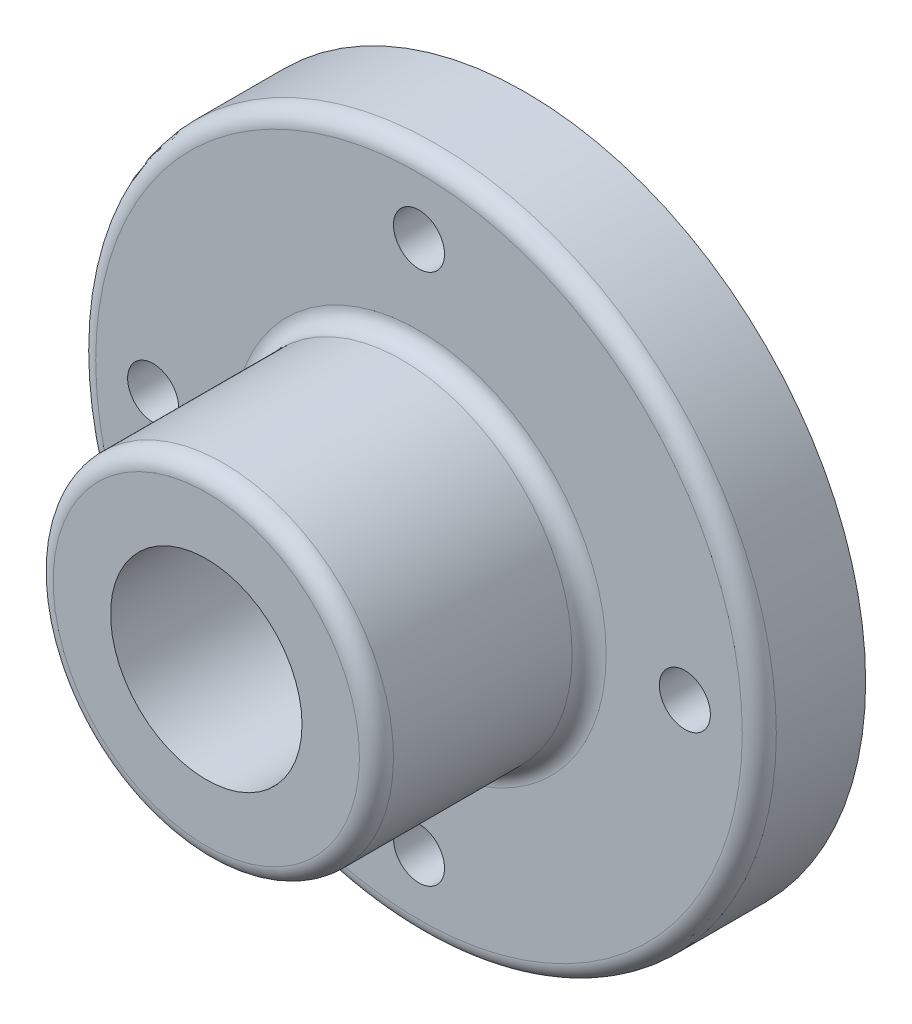
SolidWorks part; units mm, degrees
ref_plane "Plan de face" through (0, 0, 0) normal (0, 0, 1) x (1, 0, 0)
ref_plane "Plan de dessus" through (0, 0, 0) normal (0, 1, 0) x (1, 0, 0)
ref_plane "Plan de droite" through (0, 0, 0) normal (1, 0, 0) x (0, 0, -1)
sketch "Esquisse1" plane through (0, 0, 0) normal (0, 0, 1) x (1, 0, 0)
  line L0 (0, 62.5) -> (0, -62.5) construction
  line L1 (-62.5, 0) -> (62.5, 0) construction
  circle A0 centre (0, 0) radius 80
  circle A1 centre (0, 0) radius 40
  circle A2 centre (0, 0) radius 62.5
  circle A3 centre (0, 0) radius 22.5
  circle A4 centre (0, 62.5) radius 6
  circle A5 centre (-62.5, 0) radius 6
  circle A6 centre (62.5, 0) radius 6
  circle A7 centre (0, -62.5) radius 6
  point P4 (0, 0)
  point P12 (0, 0)
  point P15 (0, 0)
  point P22 (0, 0)
  point P23 (0, 0)
  dimension "D1" = 160
  dimension "D2" = 80
  dimension "D3" = 45
  dimension "D4" = 125
  dimension "D5" = 12
  dimension "D6" = 12
  dimension "D7" = 12
  dimension "D8" = 12
extrude "Base 25mm" add sketch "Esquisse1" along normal blind 25 contours A0
extrude "axe75mm" add sketch "Esquisse1<4>" along normal blind 75 contours A1
sketch "Esquisse1<4>" plane through (0, 0, 0) normal (0, 0, 1) x (1, 0, 0) same geometry as "Esquisse1"
extrude "Trou1" cut sketch "Esquisse1<5>" along normal up to next contours A4
sketch "Esquisse1<5>" plane through (0, 0, 0) normal (0, 0, 1) x (1, 0, 0) same geometry as "Esquisse1"
extrude "Trou2" cut sketch "Esquisse1<6>" along normal up to next contours A5
sketch "Esquisse1<6>" plane through (0, 0, 0) normal (0, 0, 1) x (1, 0, 0) same geometry as "Esquisse1"
extrude "Trou3&4" cut sketch "Esquisse1<7>" along normal up to next contours A6 | A7
sketch "Esquisse1<7>" plane through (0, 0, 0) normal (0, 0, 1) x (1, 0, 0) same geometry as "Esquisse1"
extrude "TrouPrincipal" cut sketch "Esquisse1<8>" along normal up to next contours A3
sketch "Esquisse1<8>" plane through (0, 0, 0) normal (0, 0, 1) x (1, 0, 0) same geometry as "Esquisse1"
fillet "Congé1" radius 4 1 edges at (40, 0, 25)
fillet "Congé2" radius 4 1 edges at (80, 0, 25)
fillet "Congé3" radius 4 1 edges at (40, 0, 75)
